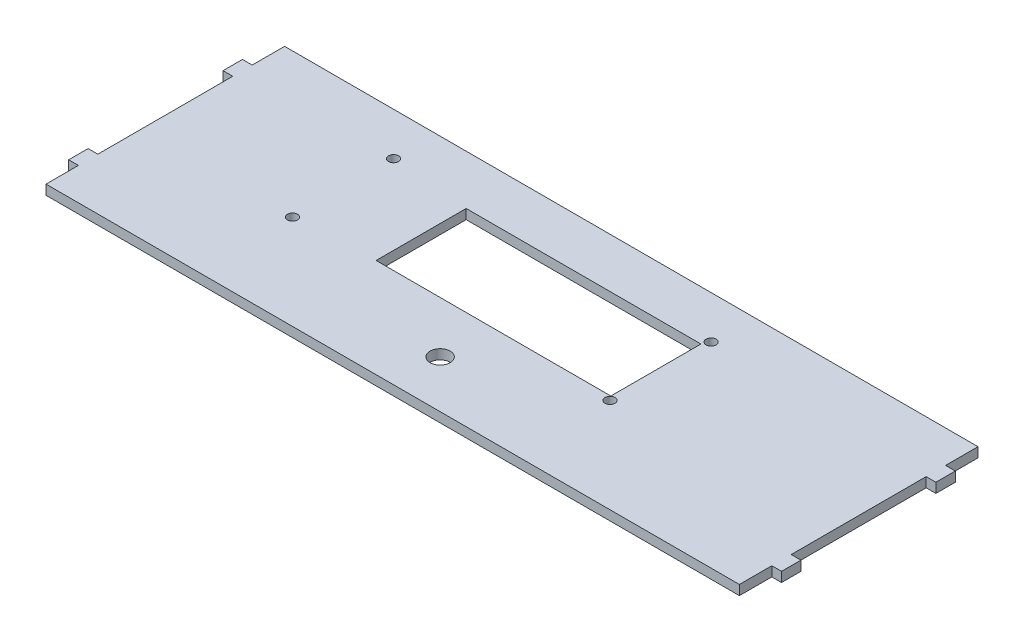
SolidWorks part; units mm, degrees
ref_plane "Alzado" through (0, 0, 0) normal (0, 0, 1) x (1, 0, 0)
ref_plane "Planta" through (0, 0, 0) normal (0, 1, 0) x (1, 0, 0)
ref_plane "Vista lateral" through (0, 0, 0) normal (1, 0, 0) x (0, 0, -1)
sketch "Croquis1" plane through (0, 0, 0) normal (0, 1, 0) x (1, 0, 0)
  line L1 (-107, 36.82) -> (107, 36.82)
  line L2 (-107, 36.82) -> (-107, -36.82)
  line L3 (-107, -36.82) -> (107, -36.82)
  line L4 (107, 36.82) -> (107, -36.82)
  line L5 (-107, 36.82) -> (107, -36.82) construction
  line L6 (-107, -36.82) -> (107, 36.82) construction
  point P0 (0, 0)
  dimension "D1" = 214
  dimension "D2" = 73.64
extrude "Saliente-Extruir1" add sketch "Croquis1" along normal blind 3
sketch "Croquis2" plane through (0, 3, 0) normal (0, 1, 0) x (1, 0, 0)
  line L0 (0, -19.08) -> (0, -25.28) construction
  line L1 (0, 36.82) -> (0, -36.82) construction
  line L8 (107, 36.82) -> (-107, 36.82) construction
  line L10 (-107, -36.82) -> (107, -36.82) construction
  circle A0 centre (0, -22.18) radius 3.1
  dimension "D1" = 6.2
  dimension "D2" = 0
  dimension "D5" = 59
sketch "Croquis3" plane through (0, 3, 0) normal (0, 1, 0) x (1, 0, 0)
  line L0 (-107, 36.82) -> (-107, -36.82) construction
  line L1 (-107, 26.82) -> (-110, 26.82)
  line L2 (-107, 26.82) -> (-107, 20.82)
  line L3 (-107, 20.82) -> (-110, 20.82)
  line L4 (-110, 26.82) -> (-110, 20.82)
  line L5 (-107, -36.82) -> (107, -36.82) construction
  line L6 (-107, -26.82) -> (-110, -26.82)
  line L7 (-107, -26.82) -> (-107, -20.82)
  line L8 (-107, -20.82) -> (-110, -20.82)
  line L9 (-110, -26.82) -> (-110, -20.82)
  line L10 (107, 36.82) -> (-107, 36.82) construction
  line L11 (107, -36.82) -> (107, 36.82) construction
  line L12 (107, 26.82) -> (110, 26.82)
  line L13 (107, 26.82) -> (107, 20.82)
  line L14 (107, 20.82) -> (110, 20.82)
  line L15 (110, 26.82) -> (110, 20.82)
  line L17 (107, -20.82) -> (110, -20.82)
  line L18 (107, -20.82) -> (107, -26.82)
  line L19 (107, -26.82) -> (110, -26.82)
  line L20 (110, -20.82) -> (110, -26.82)
  dimension "D1" = 3
  dimension "D2" = 3
  dimension "D3" = 6
  dimension "D4" = 6
  dimension "D5" = 10
  dimension "D6" = 10
  dimension "D7" = 6
  dimension "D8" = 3
  dimension "D9" = 3
  dimension "D10" = 6
  dimension "D11" = 10
  dimension "D12" = 10
extrude "Saliente-Extruir2" add sketch "Croquis3" against normal through all
extrude "Cortar-Extruir1" cut sketch "Croquis2" against normal through all
sketch "Croquis5" plane through (0, 3, 0) normal (0, 1, 0) x (1, 0, 0)
  line L1 (107, 36.82) -> (-107, 36.82) construction
  line L2 (-107, 36.82) -> (-107, 26.82) construction
  line L3 (-107, -36.82) -> (107, -36.82) construction
  line L4 (-107, 20.82) -> (-107, -20.82) construction
  line L6 (107, -20.82) -> (107, 20.82) construction
  line L7 (107, 26.82) -> (107, 36.82) construction
  circle A0 centre (-60.15, 23.605) radius 1.55
  circle A1 centre (37.85, 23.605) radius 1.55
  circle A2 centre (37.85, -7.595) radius 1.55
  circle A3 centre (-60.15, -7.595) radius 1.55
  point P2 (-107, 31.82)
  dimension "D5" = 3.1
  dimension "D6" = 3.1
  dimension "D7" = 3.1
  dimension "D8" = 3.1
  dimension "D1" = 13.215
  dimension "D2" = 46.85
  dimension "D3" = 29.225
  dimension "D4" = 46.85
  dimension "D9" = 29.225
  dimension "D10" = 69.15
  dimension "D11" = 13.215
  dimension "D12" = 69.15
extrude "Cortar-Extruir3" cut sketch "Croquis5" against normal through all
sketch "Croquis6" plane through (0, 3, 0) normal (0, 1, 0) x (1, 0, 0)
  line L0 (37.85, 23.605) -> (37.85, -7.595) construction
  line L1 (-35.65, 21.505) -> (36.8, 21.505)
  line L2 (-35.65, 21.505) -> (-35.65, -6.295)
  line L3 (-35.65, -6.295) -> (36.8, -6.295)
  line L4 (36.8, 21.505) -> (36.8, -6.295)
  line L5 (37.85, -7.595) -> (-60.15, -7.595) construction
  line L6 (-60.15, -7.595) -> (-60.15, 23.605) construction
  line L7 (-60.15, 23.605) -> (37.85, 23.605) construction
  line L8 (-35.65, 7.605) -> (36.8, 7.605) construction
  dimension "D1" = 72.45
  dimension "D2" = 27.8
  dimension "D3" = 15.2
  dimension "D4" = 24.5
extrude "Cortar-Extruir4" cut sketch "Croquis6" against normal through all
